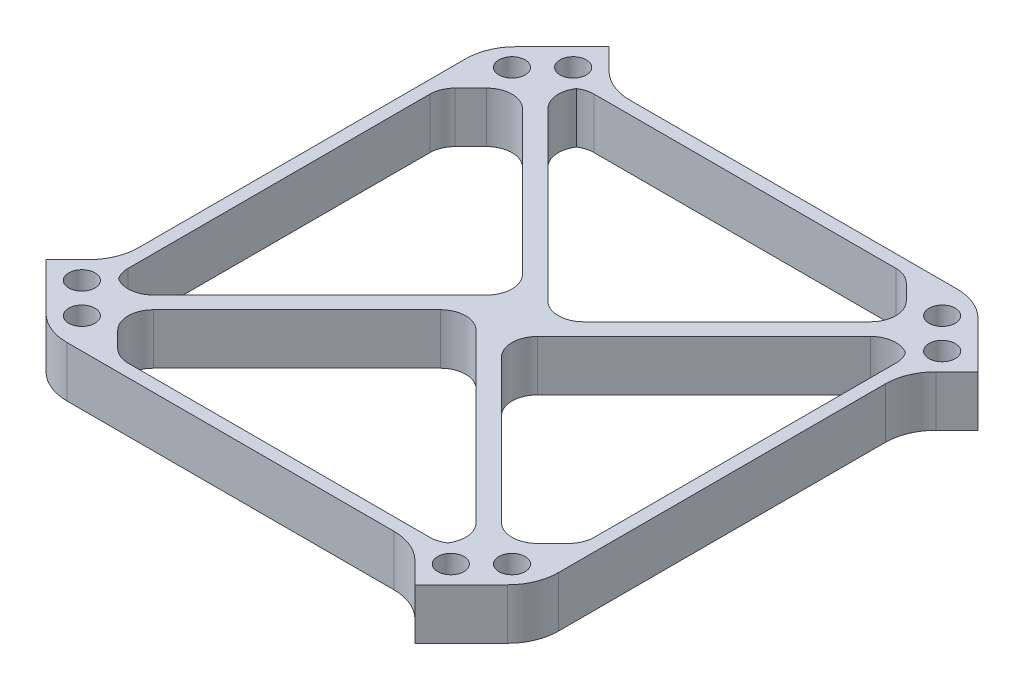
SolidWorks part; units mm, degrees
ref_plane "Front Plane" through (0, 0, 0) normal (0, 0, 1) x (1, 0, 0)
ref_plane "Top Plane" through (0, 0, 0) normal (0, 1, 0) x (1, 0, 0)
ref_plane "Right Plane" through (0, 0, 0) normal (1, 0, 0) x (0, 0, -1)
sketch "Sketch1" plane through (0, 0, 0) normal (0, 1, 0) x (1, 0, 0)
  line L0 (-55.533, 36.3909) -> (-36.3909, 55.533) construction
  line L1 (-36.3909, 55.533) -> (36.3909, 55.533) construction
  line L2 (36.3909, 55.533) -> (55.533, 36.3909) construction
  line L3 (55.533, 36.3909) -> (55.533, -36.3909) construction
  line L4 (55.533, -36.3909) -> (36.3909, -55.533) construction
  line L5 (36.3909, -55.533) -> (-36.3909, -55.533) construction
  line L6 (-36.3909, -55.533) -> (-55.533, -36.3909) construction
  line L7 (-55.533, -36.3909) -> (-55.533, 36.3909) construction
  line L8 (0, 0) -> (0, 31.0491) construction
  line L9 (0, 0) -> (32.6609, 0) construction
  line L10 (-48.4619, 43.4619) -> (-36.3909, 55.533)
  line L11 (-45.9619, -45.9619) -> (45.9619, -45.9619) construction
  line L12 (-45.9619, -45.9619) -> (-45.9619, 45.9619) construction
  line L13 (-45.9619, 45.9619) -> (45.9619, 45.9619) construction
  line L14 (45.9619, -45.9619) -> (45.9619, 45.9619) construction
  line L15 (-36.3909, 55.533) -> (-29.3198, 48.4619)
  line L16 (-29.3198, 48.4619) -> (43.4619, 48.4619)
  line L17 (43.4619, 48.4619) -> (55.533, 36.3909)
  line L18 (55.533, 36.3909) -> (48.4619, 29.3198)
  line L19 (48.4619, 29.3198) -> (48.4619, -43.4619)
  line L20 (48.4619, -43.4619) -> (36.3909, -55.533)
  line L21 (36.3909, -55.533) -> (29.3198, -48.4619)
  line L22 (29.3198, -48.4619) -> (-43.4619, -48.4619)
  line L23 (-43.4619, -48.4619) -> (-55.533, -36.3909)
  line L24 (-55.533, -36.3909) -> (-48.4619, -29.3198)
  line L25 (-48.4619, -29.3198) -> (-48.4619, 43.4619)
  point P18 (-45.9619, 45.9619)
  dimension "D1" = 65
  dimension "D2" = 10
  dimension "D3" = 2.5
extrude "Boss-Extrude1" add sketch "Sketch1" along normal blind 10
sketch "Sketch2" plane through (0, 10, 0) normal (0, 1, 0) x (1, 0, 0)
  line L0 (0, 0) -> (0, 27.7289) construction
  line L1 (48.4619, -48.4619) -> (-48.4619, -48.4619) construction
  line L2 (-48.4619, 43.4619) -> (-48.4619, -29.3198) construction
  line L3 (48.4619, 48.4619) -> (-48.4619, 48.4619) construction
  line L4 (-48.4619, -48.4619) -> (-48.4619, 48.4619) construction
  line L5 (0, 0) -> (26.129, 0) construction
  line L10 (-2.5, 4.5711) -> (-42.4264, -35.3553)
  line L11 (-45.9619, 31.8198) -> (-37.8553, 39.9264)
  line L12 (-37.8553, 39.9264) -> (-2.5, 4.5711)
  line L13 (-42.4264, -35.3553) -> (-45.9619, -31.8198)
  line L15 (43.4619, 48.4619) -> (-29.3198, 48.4619) construction
  line L16 (-43.4619, -48.4619) -> (29.3198, -48.4619) construction
  line L17 (48.4619, 48.4619) -> (48.4619, -48.4619) construction
  line L18 (48.4619, -43.4619) -> (48.4619, 29.3198) construction
  line L19 (-36.3909, 55.533) -> (-48.4619, 43.4619) construction
  line L20 (-45.9619, -31.8198) -> (-45.9619, 31.8198)
  line L21 (-48.4619, -29.3198) -> (-45.9619, -31.8198) construction
  dimension "D1" = 10
  dimension "D2" = 5
  dimension "D3" = 5
  dimension "D4" = 2.5
extrude "Cut-Extrude1" cut sketch "Sketch2" against normal through all
ref_axis "Axis2" through (0, 10.5, 0) along (0, -1, 0)
fillet "Fillet4" radius 5 5 edges at (-37.8553, 5, -39.9264) (-2.5, 5, -4.5711) (-45.9619, 5, 31.8198) (-42.4264, 5, 35.3553) (-45.9619, 5, -31.8198)
pattern_circular "CirPattern6" count 4 over 360 about axis through (0, 10.5, 0) along (0, -1, 0) of "Cut-Extrude1", "Fillet4"
fillet "Fillet5" radius 10 8 edges at (43.4619, 5, -48.4619) (-29.3198, 5, -48.4619) (-48.4619, 5, -43.4619) (-48.4619, 5, 29.3198) (-43.4619, 5, 48.4619) (29.3198, 5, 48.4619) (48.4619, 5, -29.3198) (48.4619, 5, 43.4619)
hole_wizard "#6 (0.204) Diameter Hole1" positions "Sketch3" profile "Sketch4" hole size "#6" standard "ANSI Inch" end condition through all
sketch "Sketch3" plane through (0, 10, 0) normal (0, 1, 0) x (1, 0, 0)
  line L1 (42.4264, -42.4264) -> (-42.4264, -42.4264) construction
  line L2 (42.4264, -42.4264) -> (42.4264, 42.4264) construction
  line L3 (42.4264, 42.4264) -> (-42.4264, 42.4264) construction
  line L4 (-42.4264, -42.4264) -> (-42.4264, 42.4264) construction
  line L5 (0, 0) -> (0, 27.9091) construction
  line L7 (0, 0) -> (26.5726, 0) construction
  line L9 (-36.3909, 55.533) -> (-45.533, 46.3909) construction
  line L11 (-43.4619, 48.4619) -> (-36.3909, 55.533) construction
  line L12 (-43.4619, 48.4619) -> (-36.3909, 41.3909) construction
  line L13 (-36.3909, 55.533) -> (-29.3198, 48.4619) construction
  line L16 (-36.3909, 41.3909) -> (-36.3909, 55.533) construction
  line L18 (-43.4619, 48.4619) -> (-29.3198, 48.4619) construction
  line L20 (-29.3198, 48.4619) -> (-36.3909, 41.3909) construction
  line L22 (-41.3909, 36.3909) -> (-44.4975, 33.2843) construction
  point P3 (-42.4264, 42.4264)
  point P355 (-36.3909, 48.4619)
  dimension "D1" = 5
  dimension "D2" = 60
sketch "Sketch4" plane through (-42.4264, 10, -42.4264) normal (1, 0, 0) x (0, 0, 1)
  line L0 (0, 0) -> (0, 10)
  line L1 (0, 10) -> (2.5908, 10)
  line L2 (2.5908, 10) -> (2.5908, 0)
  line L5 (2.5908, 0) -> (0, 0)
  line L11 (0, -6.35) -> (0, 107.95) construction
  dimension "Thru Hole Dia." = 5.1816
  dimension "Thru Hole Depth" = 10
pattern_circular "CirPattern7" count 4 over 360 about axis through (0, 10.5, 0) along (0, -1, 0) of "#6 (0.204) Diameter Hole1"
equation "\"TubeDiameter\" = 6.5433in"
